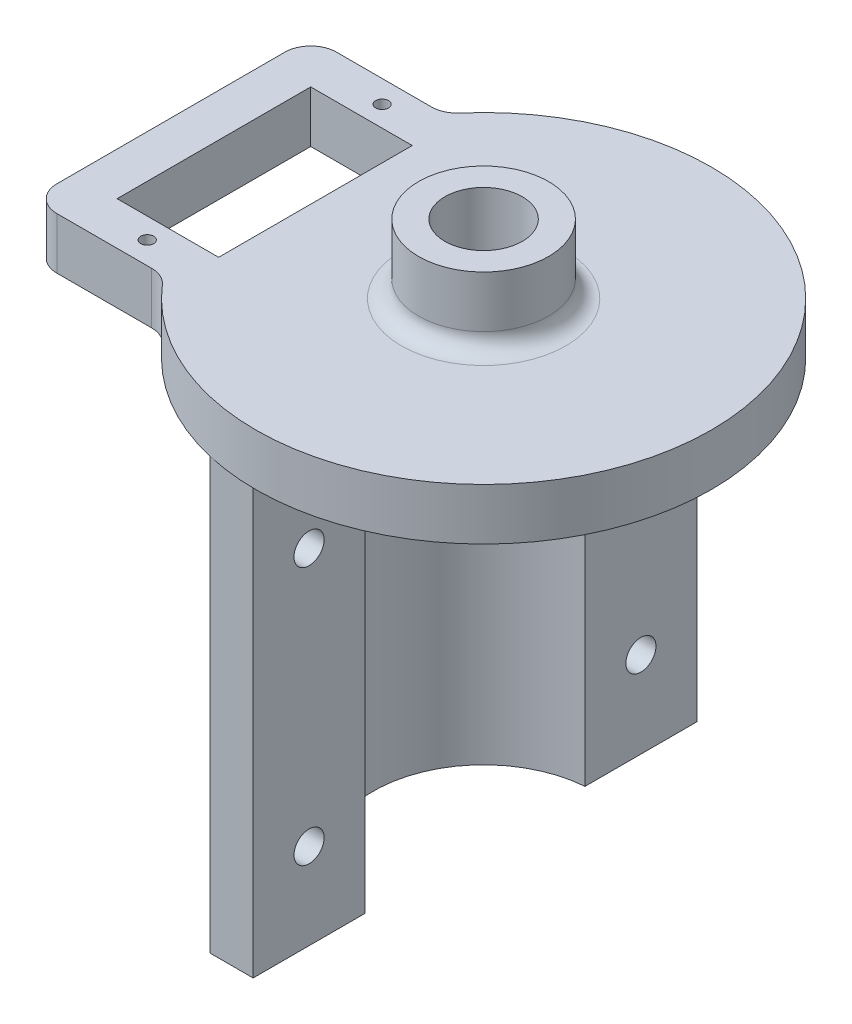
SolidWorks part; units mm, degrees
ref_plane "Front Plane" through (0, 0, 0) normal (0, 0, 1) x (1, 0, 0)
ref_plane "Top Plane" through (0, 0, 0) normal (0, 1, 0) x (1, 0, 0)
ref_plane "Right Plane" through (0, 0, 0) normal (1, 0, 0) x (0, 0, -1)
sketch "Sketch6" plane through (0, 0, 0) normal (0, -1, 0) x (1, 0, 0)
  line L5 (-1, 25.7848) -> (-1, 12.786)
  line L6 (-1, 25.7848) -> (-6, 25.7848)
  line L7 (-6, 25.7848) -> (-6, 16.7848)
  line L8 (-6, -16.7848) -> (-6, -25.7848)
  line L9 (-6, -25.7848) -> (-1, -25.7848)
  line L10 (-1, -25.7848) -> (-1, -12.786)
  line L11 (-12.825, 0) -> (-17.825, 0) construction
  arc A0 (-1, 12.786) -> (-1, -12.786) centre (0, 0) ccw
  arc A1 (-6, 16.7848) -> (-6, -16.7848) centre (0, 0) ccw
  dimension "D1" = 25.65
  dimension "D2" = 5
  dimension "D3" = 1
  dimension "D4" = 9
extrude "Boss-Extrude4" add sketch "Sketch6" along normal blind 50
sketch "Sketch7" plane through (-1, 0, 0) normal (1, 0, 0) x (0, 0, -1)
  line L0 (-19.2854, -50) -> (-19.2854, 0) construction
  line L3 (0, 0) -> (0, -50) construction
  line L6 (-25.7848, -25) -> (25.7848, -25) construction
  line L11 (-12.786, 0) -> (-25.7848, 0) construction
  line L12 (-12.786, -50) -> (-25.7848, -50) construction
  line L13 (-25.7848, -50) -> (-25.7848, 0) construction
  line L14 (25.7848, -50) -> (25.7848, 0) construction
  line L15 (-12.786, -50) -> (12.786, -50) construction
  circle A0 centre (-19.2854, -10) radius 1.75
  circle A1 centre (-19.2854, -40) radius 1.75
  circle A2 centre (19.2854, -40) radius 1.75
  circle A3 centre (19.2854, -10) radius 1.75
  dimension "D1" = 10
  dimension "D2" = 3.5
extrude "Cut-Extrude1" cut sketch "Sketch7" against normal through all
sketch "Sketch8" plane through (0, 0, 0) normal (0, 1, 0) x (1, 0, 0)
  line L0 (-25.4436, -13.65) -> (-25.4436, 13.65) construction
  line L1 (-31.3436, -11.25) -> (-19.5436, -11.25)
  line L2 (-31.3436, -11.25) -> (-31.3436, 11.25)
  line L3 (-31.3436, 11.25) -> (-19.5436, 11.25)
  line L4 (-19.5436, -11.25) -> (-19.5436, 11.25)
  line L5 (-33.3436, -16.25) -> (-22.319, -16.25)
  line L6 (-36.3436, -13.25) -> (-36.3436, 13.25)
  line L7 (-33.3436, 16.25) -> (-22.319, 16.25)
  circle A1 centre (-25.4436, 13.65) radius 0.75
  circle A2 centre (-25.4436, -13.65) radius 0.75
  arc A3 (-20.0472, -17.2906) -> (-20.0472, 17.2906) centre (0, 0) ccw
  arc A4 (-33.3436, -16.25) -> (-36.3436, -13.25) centre (-33.3436, -13.25) cw
  arc A5 (-36.3436, 13.25) -> (-33.3436, 16.25) centre (-33.3436, 13.25) cw
  arc A6 (-22.319, 16.25) -> (-20.0472, 17.2906) centre (-22.319, 19.25) ccw
  arc A7 (-22.319, -16.25) -> (-20.0472, -17.2906) centre (-22.319, -19.25) cw
  circle A8 centre (-25.4436, 5.35) radius 5.9 construction
  point P7 (-19.5436, 0)
  point P13 (-25.4436, -11.25)
  point P18 (-25.4436, 0)
  point P24 (-36.3436, 0)
  dimension "D1" = 5
  dimension "D4" = 1.5
  dimension "D7" = 5
  dimension "D8" = 3
  dimension "D9" = 3
  dimension "D10" = 11.8
  dimension "D2" = 11.8
  dimension "D3" = 22.5
  dimension "D5" = 27.3
  dimension "D6" = 26
extrude "Boss-Extrude5" add sketch "Sketch8" along normal blind 6
sketch "Sketch9" plane through (0, 6, 0) normal (0, 1, 0) x (1, 0, 0)
  circle A0 centre (0, 0) radius 7.55
  dimension "D1" = 15.1
extrude "Boss-Extrude6" add sketch "Sketch9" along normal blind 8
fillet "Fillet1" radius 2 1 edges at (0, 6, 7.55)
sketch "Sketch10" plane through (0, 14, 0) normal (0, 1, 0) x (1, 0, 0)
  circle A0 centre (0, 0) radius 4.5
  dimension "D1" = 9
extrude "Cut-Extrude2" cut sketch "Sketch10" against normal through all
